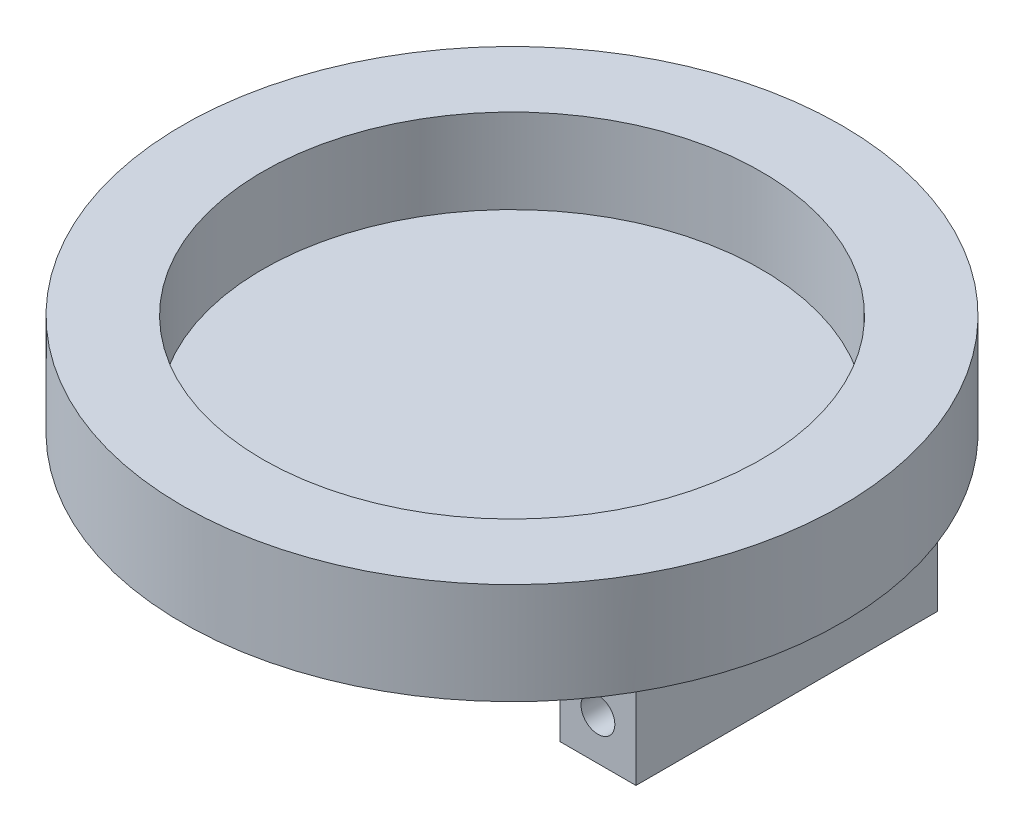
SolidWorks part; units mm, degrees
ref_plane "Front Plane" through (0, 0, 0) normal (0, 0, 1) x (1, 0, 0)
ref_plane "Top Plane" through (0, 0, 0) normal (0, 1, 0) x (1, 0, 0)
ref_plane "Right Plane" through (0, 0, 0) normal (1, 0, 0) x (0, 0, -1)
sketch "Sketch1" plane through (0, 0, 0) normal (0, 1, 0) x (1, 0, 0)
  circle A0 centre (0, 0) radius 187.325
  circle A1 centre (0, 0) radius 247.65
  dimension "D1" = 374.65
  dimension "D2" = 495.3
extrude "Boss-Extrude1" add sketch "Sketch1" along normal blind 63.5
sketch "Sketch2" plane through (0, 0, 0) normal (0, -1, 0) x (1, 0, 0)
  line L0 (-177.8, 0) -> (177.8, 0) construction
  line L1 (-206.375, 113.2367) -> (-149.225, 113.2367)
  line L2 (-206.375, 113.2367) -> (-206.375, -113.2367)
  line L3 (-206.375, -113.2367) -> (-149.225, -113.2367)
  line L4 (-149.225, 113.2367) -> (-149.225, -113.2367)
  line L5 (-206.375, 113.2367) -> (-149.225, -113.2367) construction
  line L6 (-206.375, -113.2367) -> (-149.225, 113.2367) construction
  line L7 (149.225, 113.2367) -> (206.375, 113.2367)
  line L8 (149.225, 113.2367) -> (149.225, -113.2367)
  line L9 (149.225, -113.2367) -> (206.375, -113.2367)
  line L10 (206.375, 113.2367) -> (206.375, -113.2367)
  line L11 (149.225, 113.2367) -> (206.375, -113.2367) construction
  line L12 (149.225, -113.2367) -> (206.375, 113.2367) construction
  circle A0 centre (0, 0) radius 187.325 construction
  circle A1 centre (0, 0) radius 247.65
  circle A2 centre (0, 0) radius 247.65 construction
  point P0 (-177.8, 0)
  point P5 (177.8, 0)
  point P11 (0, 0)
  circle M7 centre (0, 0) radius 247.65
  circle M8 centre (0, 0) radius 187.325
  dimension "D1" = 57.15
  dimension "D2" = 355.6
extrude "Boss-Extrude2" add sketch "Sketch2" along normal blind 12.7 contours L8 L4 M8 | L4 M8 | L8 M8 | L10 L7 L9 M8 | L7 L10 L9 L3 L2 L1 M7 M8 | L2 L3 L1 M8 region at (-188.7862, 0, 0) region at (0, 0, 0) region at (-164.6062, 0, 0) region at (164.6062, 0, 0) region at (188.7862, 0, 0) region at (-240.6454, 0, 0)
extrude "Boss-Extrude3" add sketch "Sketch2<3>" along normal blind 69.85 from surface contours L4 M8 | L2 L3 L1 M8 | L10 L7 L9 M8 | L8 M8 region at (-188.7862, 0, 0) region at (-164.6062, 0, 0) region at (164.6062, 0, 0) region at (188.7862, 0, 0) starting at face at (0, -12.7, -247.65)
sketch "Sketch2<3>" plane through (0, 0, 0) normal (0, -1, 0) x (1, 0, 0) same geometry as "Sketch2"
sketch "Sketch4" plane through (0, 0, 113.2367) normal (0, 0, 1) x (1, 0, 0)
  line L0 (206.375, -82.55) -> (149.225, -82.55) construction
  line L1 (-149.225, -82.55) -> (-206.375, -82.55) construction
  circle A0 centre (177.8, -50.8) radius 12.7
  circle A1 centre (-177.8, -50.8) radius 12.7
  point P6 (177.8, -82.55)
  point P9 (-177.8, -82.55)
  point P10 (177.8, -57.4327)
  dimension "D1" = 25.4
  dimension "D2" = 31.75
extrude "Cut-Extrude1" cut sketch "Sketch4" against normal up to next
